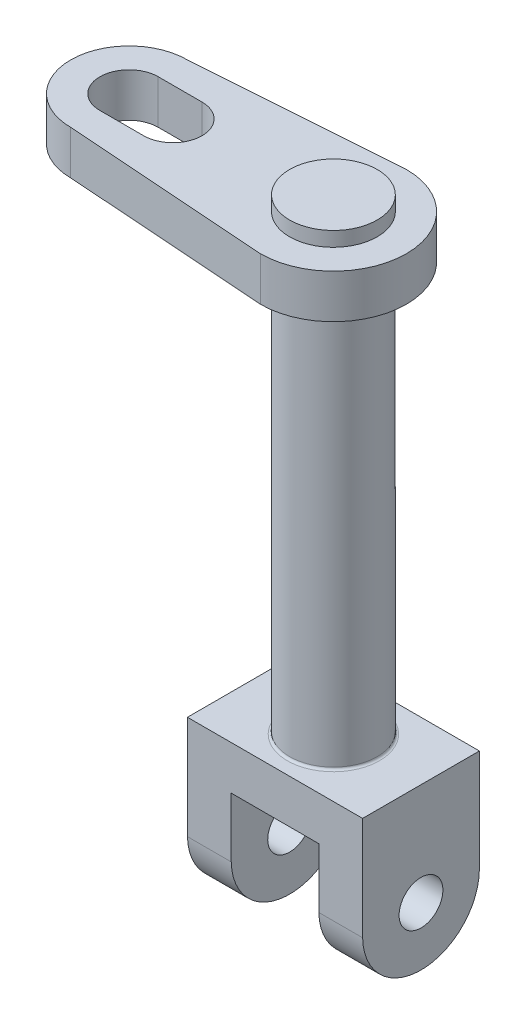
SolidWorks part; units mm, degrees
ref_plane "Front Plane" through (0, 0, 0) normal (0, 0, 1) x (1, 0, 0)
ref_plane "Top Plane" through (0, 0, 0) normal (0, 1, 0) x (1, 0, 0)
ref_plane "Right Plane" through (0, 0, 0) normal (1, 0, 0) x (0, 0, -1)
sketch "Sketch1" plane through (0, 0, 0) normal (1, 0, 0) x (0, 0, -1)
  line L0 (9.525, 0) -> (-9.525, 0)
  line L1 (-9.525, 0) -> (-9.525, -17.4625)
  line L2 (-9.525, -17.4625) -> (-4.7625, -17.4625)
  line L3 (-4.7625, -17.4625) -> (-4.7625, -4.7625)
  line L4 (-4.7625, -4.7625) -> (4.7625, -4.7625)
  line L5 (0, 0) -> (0, -11.6458) construction
  line L6 (9.525, -17.4625) -> (4.7625, -17.4625)
  line L7 (4.7625, -17.4625) -> (4.7625, -4.7625)
  line L8 (9.525, 0) -> (9.525, -17.4625)
  point P12 (0, -4.7625)
  dimension "D1" = 4.7625
  dimension "D2" = 4.7625
  dimension "D3" = 4.7625
  dimension "D4" = 17.4625
extrude "Boss-Extrude1" add sketch "Sketch1" along normal blind 12.7
sketch "Sketch2" plane through (0, 0, 9.525) normal (0, 0, 1) x (1, 0, 0)
  line L0 (12.7, -17.4625) -> (0, -17.4625) construction
  line L2 (0, -11.1125) -> (0, -17.4625)
  line L3 (0, -17.4625) -> (12.7, -17.4625)
  line L4 (12.7, -17.4625) -> (12.7, -11.1125)
  line L5 (0.0013, -11.2421) -> (-4.1991, -11.285)
  arc A0 (0, -11.1125) -> (12.7, -11.1125) centre (6.35, -11.1125) ccw
  point P2 (6.35, -17.4625)
  line M4 (0, -17.4625) -> (12.7, -17.4625)
  line M5 (12.7, -17.4625) -> (12.7, 0)
  dimension "D1" = 12.7
extrude "Cut-Extrude1" cut sketch "Sketch2" against normal through all both and the other way through all contours A0 L5 L2 M4 | A0 L3 M5 region at (11.2816, -16.0441, 9.525) region at (1.4184, -16.0441, 9.525)
sketch "Sketch3" plane through (0, 0, -9.525) normal (0, 0, -1) x (-1, 0, 0)
  circle A0 centre (-6.35, -11.1125) radius 2.3813
extrude "Cut-Extrude2" cut sketch "Sketch3" against normal through all both and the other way through all
sketch "Sketch4" plane through (0, 0, 0) normal (0, 1, 0) x (1, 0, 0)
  circle A0 centre (6.35, 0) radius 4.7625
extrude "Boss-Extrude2" add sketch "Sketch4" along normal blind 44.45
sketch "Sketch5" plane through (0, 44.45, 0) normal (0, 1, 0) x (1, 0, 0)
  line L0 (-11.1125, 0) -> (-15.875, 0) construction
  line L2 (-11.1125, -3.175) -> (-15.875, -3.175)
  line L3 (-11.1125, 3.175) -> (-15.875, 3.175)
  line L5 (-15.875, 6.35) -> (6.35, 7.9375)
  line L6 (6.35, -7.9375) -> (-15.875, -6.35)
  arc A0 (6.35, -7.9375) -> (6.35, 7.9375) centre (6.35, 0) ccw
  arc A1 (-11.1125, -3.175) -> (-11.1125, 3.175) centre (-11.1125, 0) ccw
  arc A2 (-15.875, 3.175) -> (-15.875, -3.175) centre (-15.875, 0) ccw
  arc A3 (-15.875, 6.35) -> (-15.875, -6.35) centre (-15.875, 0) ccw
  arc A4 (-10.3187, -3.0742) -> (-10.3187, 3.0742) centre (-15.875, 0) ccw
  point P8 (-13.4938, 0)
  circle M9 centre (6.35, 0) radius 4.7625
  dimension "D1" = 22.225
  dimension "D3" = 3.175
  dimension "D2" = 4.7625
extrude "Boss-Extrude3" add sketch "Sketch5" along normal blind 4.7625 contours L5 A3 L6 A0 A2 L3 A1 L2 M9 | M9 region at (-3.499, 44.45, 0) region at (6.35, 44.45, 0)
sketch "Sketch6" plane through (0, 49.2125, 0) normal (0, 1, 0) x (1, 0, 0)
  circle A1 centre (6.35, 0) radius 4.7625
  circle A2 centre (6.35, 0) radius 4.7625
  dimension "D1" = 0
extrude "Boss-Extrude4" add sketch "Sketch6" along normal blind 1.5875
sketch "Sketch7" plane through (0, -4.7625, 0) normal (0, -1, 0) x (1, 0, 0)
  circle A0 centre (6.3507, 0) radius 3.175
  dimension "D1" = 6.35
extrude "Cut-Extrude3" cut sketch "Sketch7" against normal blind 4.7625
fillet "Fillet1" radius 0.254 2 edges at (6.35, 0, 4.7625) (6.35, 44.45, 4.7625)
split "Split2" bodies to split 107 resulting bodies 113 114 split by face at (6.35, 0, -5.0165)
move or copy body "Body-Move/Copy4" bodies to move or copy 114 copy no rotation origin (6.35, 0, 0) rotation axis (0, 1, 0) rotation angle 90
